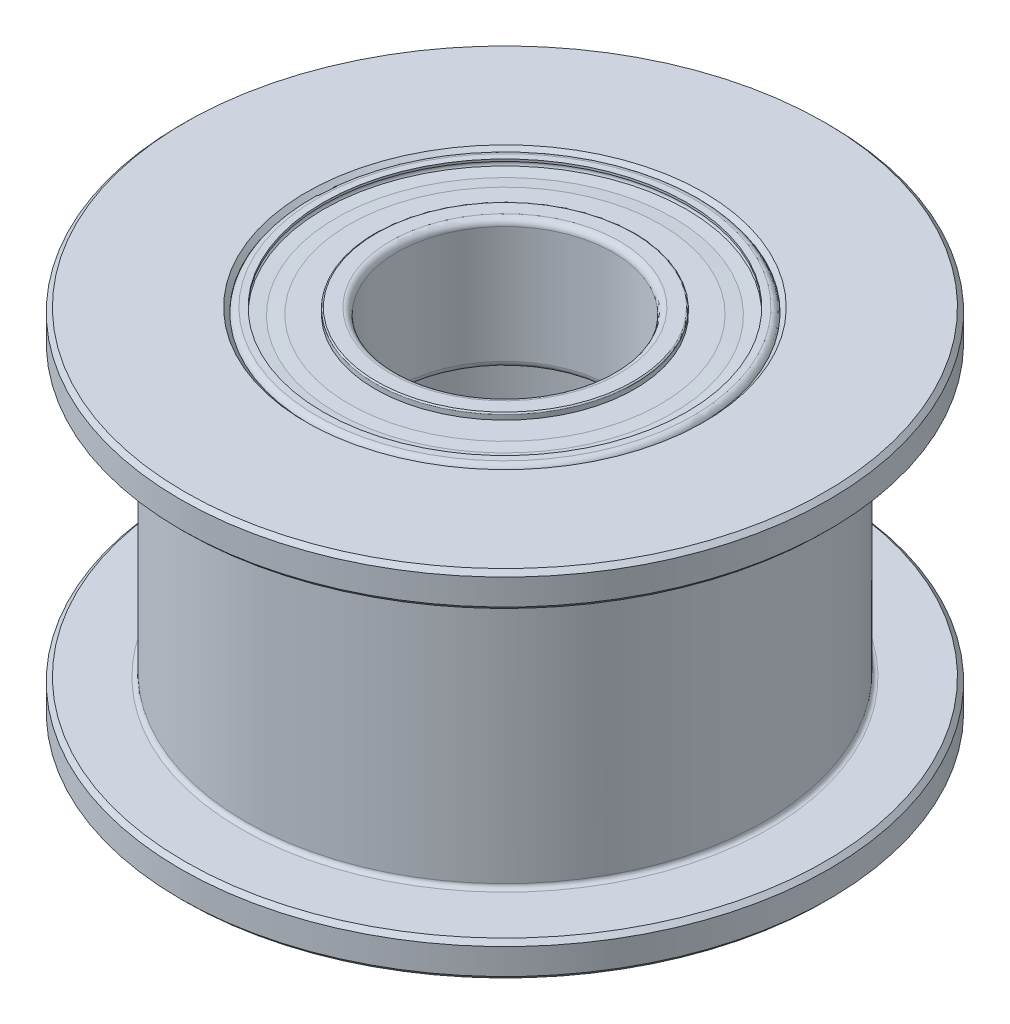
SolidWorks part; units mm, degrees
material "6061-T6 (SS)"
ref_plane "Přední rovina" through (0, 0, 0) normal (0, 0, 1) x (1, 0, 0)
ref_plane "Horní rovina" through (0, 0, 0) normal (0, 1, 0) x (1, 0, 0)
ref_plane "Pravá rovina" through (0, 0, 0) normal (1, 0, 0) x (0, 0, -1)
sketch "Skica1" plane through (0, 0, 0) normal (0, 0, 1) x (1, 0, 0)
  line L0 (4.5, 8.2) -> (7.5, 8.2)
  line L1 (7.5, 8.2) -> (7.5, 7.4)
  line L2 (7.5, 7.4) -> (6, 7.4)
  line L3 (6, 7.4) -> (6, 0.8)
  line L4 (6, 0.8) -> (7.5, 0.8)
  line L5 (7.5, 0.8) -> (7.5, 0)
  line L6 (7.5, 0) -> (4.5, 0)
  line L8 (4.5, 8.2) -> (4.5, 5.2)
  line L9 (4.5, 5.2) -> (3.5, 5.2)
  line L10 (3.5, 5.2) -> (3.5, 3)
  line L11 (3.5, 3) -> (4.5, 3)
  line L12 (4.5, 3) -> (4.5, 0)
  line L13 (0, 0) -> (0, -4.1646) construction
  dimension "D1" = 0.8
  dimension "D2" = 6.6
  dimension "D3" = 4.5
  dimension "D4" = 3.5
  dimension "D5" = 6
  dimension "D6" = 3
  dimension "D7" = 7.5
revolve "Rotovat1" add sketch "Skica1" angle 360 about L13
chamfer "Zkosení1" distance 0.1 angle 45 8 edges at (0, 3, 3.5) (0, 0, 4.5) (0, 5.2, 3.5) (0, 0, 7.5) (0, 0.8, 7.5) (0, 7.4, 7.5) (0, 8.2, 7.5) (0, 8.2, 4.5)
fillet "Zaoblit1" radius 0.1 4 edges at (0, 3, 4.5) (0, 0.8, 6) (0, 7.4, 6) (0, 5.2, 4.5)
sketch "Skica4" plane through (0, 0, 0) normal (0, 0, 1) x (1, 0, 0)
  line L0 (4.5, 8.05) -> (4.5, 5.35)
  line L1 (4.35, 5.2) -> (4.2, 5.2)
  line L2 (4.2, 5.2) -> (4.2, 5.25)
  line L3 (3.85, 5.4828) -> (4.2132, 5.429)
  line L4 (3.85, 5.4828) -> (3.85, 6.2528)
  line L5 (3.85, 7.1472) -> (3.85, 7.9172)
  line L6 (3.85, 7.9172) -> (4.2132, 7.971)
  line L7 (4.35, 8.2) -> (4.2, 8.2)
  line L8 (4.2, 8.2) -> (4.2, 8.15)
  line L9 (0, 0) -> (0, 18.4294) construction
  line L10 (4.4, 5.2) -> (-4.4, 5.2) construction
  arc A0 (4.35, 8.2) -> (4.5, 8.05) centre (4.35, 8.05) cw
  arc A1 (4.35, 5.2) -> (4.5, 5.35) centre (4.35, 5.35) ccw
  arc A2 (4.2, 8.15) -> (4.2132, 7.971) centre (4.2, 8.06) cw
  arc A3 (3.85, 7.1472) -> (3.85, 6.2528) centre (3.45, 6.7) cw
  arc A4 (4.2, 5.25) -> (4.2132, 5.429) centre (4.2, 5.34) ccw
  point P26 (4.5, 6.7)
  point P29 (4.275, 5.2)
  dimension "D3" = 0.09
  dimension "D6" = 0.15
  dimension "D7" = 0.6
  dimension "D1" = 4.5
  dimension "D2" = 3.85
  dimension "D4" = 0.05
  dimension "D5" = 0.15
  dimension "D8" = 0.77
  dimension "D9" = 3
  dimension "D10" = 1.05
revolve "Rotovat2" add sketch "Skica4" angle 360 about L9
sketch "Skica5" plane through (0, 0, 0) normal (0, 0, 1) x (1, 0, 0)
  line L0 (2.5, 8.05) -> (2.5, 5.35)
  line L1 (2.65, 8.2) -> (2.97, 8.2)
  line L2 (3, 8.17) -> (3, 8.06)
  line L3 (3, 8.06) -> (3.6, 8.06)
  line L4 (3.6, 8.06) -> (3.9, 8.04)
  line L5 (3.9, 8.04) -> (4.2, 8.06)
  line L6 (4.2, 8.06) -> (4.2, 8.01)
  line L7 (4.2, 8.01) -> (3.9, 7.97)
  line L8 (3.9, 7.97) -> (3.6, 7.97)
  line L9 (3.6, 7.97) -> (3, 8.01)
  line L10 (3, 8.01) -> (3, 7.0969)
  line L11 (2.65, 5.2) -> (2.97, 5.2)
  line L12 (0, 0) -> (0, 20.363) construction
  line L13 (3, 5.23) -> (3, 5.34)
  line L21 (3, 5.39) -> (3, 6.3031)
  line L22 (3, 5.34) -> (3.6, 5.34)
  line L23 (3.6, 5.34) -> (3.8962, 5.3917)
  line L24 (3.8962, 5.3917) -> (4.1924, 5.34)
  line L25 (4.1924, 5.34) -> (4.1924, 5.39)
  line L26 (4.1924, 5.39) -> (3.8975, 5.4581)
  line L27 (3.8975, 5.4581) -> (3.5975, 5.4581)
  line L28 (3.5975, 5.4581) -> (3, 5.39)
  line L29 (-4.2, 5.2) -> (4.2, 5.2) construction
  arc A0 (2.65, 5.2) -> (2.5, 5.35) centre (2.65, 5.35) cw
  arc A1 (2.65, 8.2) -> (2.5, 8.05) centre (2.65, 8.05) ccw
  arc A2 (3, 8.17) -> (2.97, 8.2) centre (2.97, 8.17) ccw
  arc A3 (3, 5.23) -> (2.97, 5.2) centre (2.97, 5.23) cw
  arc A4 (3, 7.0969) -> (3, 6.3031) centre (3.45, 6.7) ccw
  dimension "D3" = 0.15
  dimension "D4" = 0.11
  dimension "D5" = 0.03
  dimension "D7" = 0.6
  dimension "D1" = 2.5
  dimension "D2" = 3
  dimension "D6" = 0.6
  dimension "D8" = 0.95
  dimension "D9" = 3
  dimension "D10" = 1.2
  dimension "D11" = 0.3
  dimension "D12" = 0.05
  dimension "D13" = 0.9
  dimension "D14" = 0.6
  dimension "D15" = 0.09
  dimension "D16" = 0.05
  dimension "D17" = 0.05
revolve "Rotovat3" add sketch "Skica5" angle 360 about L12
sketch "Skica6" plane through (0, 0, 0) normal (0, 0, 1) x (1, 0, 0)
  line L0 (3.45, 7.3) -> (3.45, 6.1)
  line L4 (-4.2, 5.2) -> (4.2, 5.2) construction
  arc A0 (3.45, 7.3) -> (3.45, 6.1) centre (3.45, 6.7) cw
  dimension "D1" = 0.6
  dimension "D2" = 1.5
  dimension "D3" = 3.45
revolve "Rotovat4" add sketch "Skica6" angle 360 about L0
pattern_circular "Kruhové pole1" count 8 over 360 about axis through (0, 0, 0) along (0, 1, 0) of bodies 105
sketch "Skica7" plane through (0, 0, 0) normal (0, 0, 1) x (1, 0, 0)
  line L0 (4.5, 2.85) -> (4.5, 0.15)
  line L1 (4.35, 0) -> (4.2, 0)
  line L2 (4.2, 0) -> (4.2, 0.05)
  line L3 (3.85, 0.2828) -> (4.2132, 0.229)
  line L4 (3.85, 0.2828) -> (3.85, 1.0528)
  line L5 (3.85, 1.9472) -> (3.85, 2.7172)
  line L6 (3.85, 2.7172) -> (4.2132, 2.771)
  line L7 (4.35, 3) -> (4.2, 3)
  line L8 (4.2, 3) -> (4.2, 2.95)
  line L9 (0, 0) -> (0, 11.2374) construction
  arc A0 (4.35, 3) -> (4.5, 2.85) centre (4.35, 2.85) cw
  arc A1 (4.35, 0) -> (4.5, 0.15) centre (4.35, 0.15) ccw
  arc A2 (4.2, 2.95) -> (4.2132, 2.771) centre (4.2, 2.86) cw
  arc A3 (3.85, 1.9472) -> (3.85, 1.0528) centre (3.45, 1.5) cw
  arc A4 (4.2, 0.05) -> (4.2132, 0.229) centre (4.2, 0.14) ccw
  point P19 (4.5, 1.5)
  point P20 (4.275, 0)
  dimension "D1" = 0.09
  dimension "D4" = 0.15
  dimension "D5" = 0.6
  dimension "D2" = 0.05
  dimension "D3" = 0.15
  dimension "D6" = 0.77
  dimension "D7" = 3
  dimension "D8" = 1.05
  dimension "D9" = 4.5
  dimension "D10" = 3.85
revolve "Rotovat5" add sketch "Skica7" angle 360 about L9
sketch "Skica8" plane through (0, 0, 0) normal (0, 0, 1) x (1, 0, 0)
  line L0 (2.5, 2.85) -> (2.5, 0.15)
  line L1 (2.65, 3) -> (2.97, 3)
  line L2 (3, 2.97) -> (3, 2.86)
  line L3 (3, 2.86) -> (3.6, 2.86)
  line L4 (3.6, 2.86) -> (3.9, 2.84)
  line L5 (3.9, 2.84) -> (4.2, 2.86)
  line L6 (4.2, 2.86) -> (4.2, 2.81)
  line L7 (4.2, 2.81) -> (3.9, 2.77)
  line L8 (3.9, 2.77) -> (3.6, 2.77)
  line L9 (3.6, 2.77) -> (3, 2.81)
  line L10 (3, 2.81) -> (3, 1.8969)
  line L11 (2.65, 0) -> (2.97, 0)
  line L12 (3, 0.03) -> (3, 0.14)
  line L13 (3, 0.19) -> (3, 1.1031)
  line L14 (3, 0.14) -> (3.6, 0.14)
  line L15 (3.6, 0.14) -> (3.8962, 0.1917)
  line L16 (3.8962, 0.1917) -> (4.1924, 0.14)
  line L17 (4.1924, 0.14) -> (4.1924, 0.19)
  line L18 (4.1924, 0.19) -> (3.8975, 0.2581)
  line L19 (3.8975, 0.2581) -> (3.5975, 0.2581)
  line L20 (3.5975, 0.2581) -> (3, 0.19)
  line L21 (0, 0) -> (0, -2.9362) construction
  arc A0 (2.65, 0) -> (2.5, 0.15) centre (2.65, 0.15) cw
  arc A1 (2.65, 3) -> (2.5, 2.85) centre (2.65, 2.85) ccw
  arc A2 (3, 2.97) -> (2.97, 3) centre (2.97, 2.97) ccw
  arc A3 (3, 0.03) -> (2.97, 0) centre (2.97, 0.03) cw
  arc A4 (3, 1.8969) -> (3, 1.1031) centre (3.45, 1.5) ccw
  dimension "D1" = 0.15
  dimension "D2" = 0.03
  dimension "D5" = 0.6
  dimension "D3" = 0.11
  dimension "D4" = 0.6
  dimension "D6" = 0.95
  dimension "D7" = 3
  dimension "D8" = 1.2
  dimension "D9" = 0.3
  dimension "D10" = 0.05
  dimension "D11" = 0.9
  dimension "D12" = 0.6
  dimension "D13" = 0.09
  dimension "D14" = 0.05
  dimension "D15" = 0.05
  dimension "D16" = 2.5
  dimension "D17" = 3
revolve "Rotovat6" add sketch "Skica8" angle 360 about L21
sketch "Skica9" plane through (0, 0, 0) normal (0, 0, 1) x (1, 0, 0)
  line L0 (3.45, 2.1) -> (3.45, 0.9)
  line L1 (0, -2.351) -> (0, 5.6956) construction
  arc A0 (3.45, 2.1) -> (3.45, 0.9) centre (3.45, 1.5) cw
  dimension "D1" = 0.6
  dimension "D2" = 3.45
  dimension "D3" = 1.5
revolve "Rotovat7" add sketch "Skica9" angle 360 about L0
pattern_circular "Kruhové pole3" count 8 over 360 about axis through (0, 0, 0) along (0, 1, 0) reverse direction yes of bodies 123
